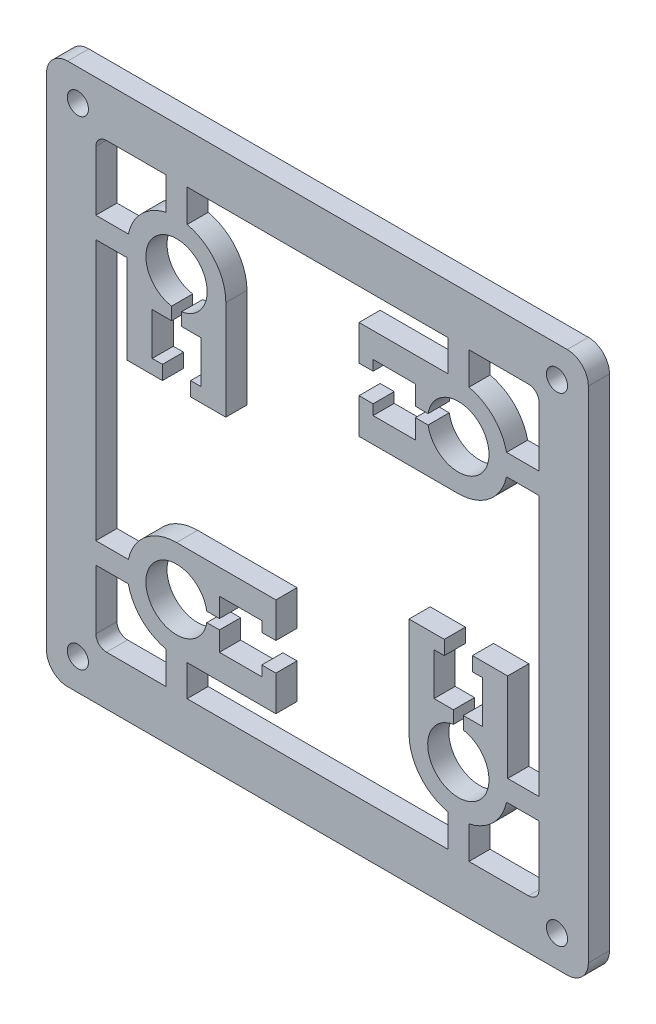
SolidWorks part; units mm, degrees
ref_plane "前基準面" through (0, 0, 0) normal (0, 0, 1) x (1, 0, 0)
ref_plane "上基準面" through (0, 0, 0) normal (0, 1, 0) x (1, 0, 0)
ref_plane "右基準面" through (0, 0, 0) normal (1, 0, 0) x (0, 0, -1)
other "mode"
sketch "草圖1" plane through (0, 0, 0) normal (0, 0, 1) x (1, 0, 0)
  line L0 (0, 0) -> (0, -50.7538) construction
  line L1 (-35.45, 38.45) -> (35.45, 38.45)
  line L2 (-38.45, 35.45) -> (-38.45, -35.45)
  line L3 (-35.45, -38.45) -> (35.45, -38.45)
  line L4 (38.45, 35.45) -> (38.45, -35.45)
  line L5 (0, 0) -> (-82.4302, 0) construction
  line L6 (-29.95, -31.45) -> (-21.5, -31.45)
  line L7 (31.45, 29.95) -> (31.45, 21.5)
  line L8 (-29.95, 31.45) -> (-21.5, 31.45)
  line L9 (-31.45, 29.95) -> (-31.45, 21.5)
  line L10 (-31.45, 31.45) -> (-31.45, -31.45) construction
  line L11 (-31.45, -31.45) -> (31.45, -31.45) construction
  line L12 (31.45, 31.45) -> (31.45, -31.45) construction
  line L13 (-31.45, 31.45) -> (31.45, 31.45) construction
  line L14 (-15.65, 20) -> (18.5, 20) construction
  line L15 (-20, 20) -> (-20, 24.0832) construction
  line L16 (20, 20) -> (20, 43.9064) construction
  line L17 (-18.5, 31.45) -> (18.5, 31.45)
  line L18 (-31.45, 18.5) -> (-31.45, -18.5)
  line L19 (-21.5, 31.45) -> (-21.5, 26.8374)
  line L20 (-13.1626, 18.5) -> (13.1626, 18.5)
  line L21 (-18.5, 31.45) -> (-18.5, 26.8374)
  line L22 (-31.45, 21.5) -> (-26.8374, 21.5)
  line L23 (-13.1626, 21.5) -> (13.1626, 21.5)
  line L24 (-31.45, 18.5) -> (-26.8374, 18.5)
  line L25 (26.8374, 18.5) -> (31.45, 18.5)
  line L26 (18.5, 13.1626) -> (18.5, -13.1626)
  line L27 (18.5, 26.8374) -> (18.5, 31.45)
  line L28 (31.45, 18.5) -> (31.45, -18.5)
  line L29 (21.5, 26.8374) -> (21.5, 31.45)
  line L30 (21.5, 31.45) -> (29.95, 31.45)
  line L31 (26.8374, 21.5) -> (31.45, 21.5)
  line L32 (-31.45, -18.5) -> (-26.8374, -18.5)
  line L33 (-31.45, -21.5) -> (-26.8374, -21.5)
  line L34 (-21.5, -31.45) -> (-21.5, -26.8374)
  line L35 (-18.5, -31.45) -> (-18.5, -26.8374)
  line L36 (-13.1626, -18.5) -> (13.1626, -18.5)
  line L37 (-13.1626, -21.5) -> (13.1626, -21.5)
  line L38 (18.5, -26.8374) -> (18.5, -31.45)
  line L39 (21.5, -26.8374) -> (21.5, -31.45)
  line L40 (26.8374, -21.5) -> (31.45, -21.5)
  line L41 (26.8374, -18.5) -> (31.45, -18.5)
  line L42 (-31.45, -21.5) -> (-31.45, -29.95)
  line L43 (-20, 38.45) -> (-20, 44.9928) construction
  line L44 (-18.5, -31.45) -> (18.5, -31.45)
  line L45 (-21.5, 13.1626) -> (-21.5, -13.1626)
  line L46 (21.5, -31.45) -> (29.95, -31.45)
  line L47 (-18.5, 13.1626) -> (-18.5, -13.1626)
  line L48 (31.45, -21.5) -> (31.45, -29.95)
  line L49 (5.975, 5.975) -> (5.975, -5.975)
  line L51 (21.5, 13.1626) -> (21.5, -13.1626)
  line L52 (-5.975, 5.975) -> (5.975, 5.975)
  line L53 (-5.975, 5.975) -> (-5.975, -5.975)
  line L54 (-5.975, -5.975) -> (5.975, -5.975)
  arc A0 (-21.5, 24.0832) -> (-24.0832, 21.5) centre (-20, 20) ccw construction
  arc A1 (-24.0832, -21.5) -> (-21.5, -24.0832) centre (-20, -20) ccw construction
  arc A2 (18.5, 24.0832) -> (15.9168, 21.5) centre (20, 20) ccw construction
  arc A3 (15.9168, -21.5) -> (18.5, -24.0832) centre (20, -20) ccw construction
  arc A4 (35.45, 38.45) -> (38.45, 35.45) centre (35.45, 35.45) cw
  arc A5 (35.45, -38.45) -> (38.45, -35.45) centre (35.45, -35.45) ccw
  arc A6 (-38.45, -35.45) -> (-35.45, -38.45) centre (-35.45, -35.45) ccw
  arc A7 (-35.45, 38.45) -> (-38.45, 35.45) centre (-35.45, 35.45) ccw
  circle A8 centre (-34, 34) radius 1.5
  circle A9 centre (34, 34) radius 1.5
  circle A10 centre (34, -34) radius 1.5
  circle A11 centre (-34, -34) radius 1.5
  arc A12 (31.45, 29.95) -> (29.95, 31.45) centre (29.95, 29.95) ccw
  arc A13 (-29.95, 31.45) -> (-31.45, 29.95) centre (-29.95, 29.95) ccw
  arc A14 (-24.0832, 18.5) -> (-21.5, 15.9168) centre (-20, 20) ccw construction
  arc A15 (29.95, -31.45) -> (31.45, -29.95) centre (29.95, -29.95) ccw
  arc A16 (-31.45, -29.95) -> (-29.95, -31.45) centre (-29.95, -29.95) ccw
  arc A17 (-31.45, -31.45) -> (-31.45, -31.45) centre (-31.45, -31.45) ccw construction
  arc A18 (31.45, -31.45) -> (31.45, -31.45) centre (31.45, -31.45) ccw construction
  arc A19 (31.45, 31.45) -> (31.45, 31.45) centre (31.45, 31.45) cw construction
  arc A20 (-31.45, 31.45) -> (-31.45, 31.45) centre (-31.45, 31.45) ccw construction
  arc A21 (-15.9168, 21.5) -> (-18.5, 24.0832) centre (-20, 20) ccw construction
  arc A22 (24.0832, 21.5) -> (21.5, 24.0832) centre (20, 20) ccw construction
  arc A23 (15.9168, 18.5) -> (18.5, 15.9168) centre (20, 20) ccw construction
  arc A24 (-18.5, -24.0832) -> (-15.9168, -21.5) centre (-20, -20) ccw construction
  arc A25 (-15.9168, -18.5) -> (-18.5, -15.9168) centre (-20, -20) ccw construction
  arc A26 (21.5, -24.0832) -> (24.0832, -21.5) centre (20, -20) ccw construction
  arc A27 (24.0832, -18.5) -> (21.5, -15.9168) centre (20, -20) ccw construction
  arc A28 (-21.5, -15.9168) -> (-24.0832, -18.5) centre (-20, -20) ccw construction
  arc A29 (18.5, -15.9168) -> (15.9168, -18.5) centre (20, -20) ccw construction
  arc A30 (21.5, 15.9168) -> (24.0832, 18.5) centre (20, 20) ccw construction
  arc A31 (-18.5, 15.9168) -> (-15.9168, 18.5) centre (-20, 20) ccw construction
  arc A32 (-21.5, 26.8374) -> (-26.8374, 21.5) centre (-20, 20) ccw
  arc A33 (-13.1626, 21.5) -> (-18.5, 26.8374) centre (-20, 20) ccw
  arc A34 (-26.8374, 18.5) -> (-21.5, 13.1626) centre (-20, 20) ccw
  arc A35 (-18.5, 13.1626) -> (-13.1626, 18.5) centre (-20, 20) ccw
  circle A36 centre (-20, 20) radius 4.35
  arc A37 (26.8374, 21.5) -> (21.5, 26.8374) centre (20, 20) ccw
  arc A38 (-18.5, -26.8374) -> (-13.1626, -21.5) centre (-20, -20) ccw
  arc A39 (21.5, -26.8374) -> (26.8374, -21.5) centre (20, -20) ccw
  arc A40 (-21.5, -13.1626) -> (-26.8374, -18.5) centre (-20, -20) ccw
  arc A41 (-13.1626, -18.5) -> (-18.5, -13.1626) centre (-20, -20) ccw
  arc A42 (-26.8374, -21.5) -> (-21.5, -26.8374) centre (-20, -20) ccw
  arc A43 (26.8374, -18.5) -> (21.5, -13.1626) centre (20, -20) ccw
  arc A44 (18.5, -13.1626) -> (13.1626, -18.5) centre (20, -20) ccw
  arc A45 (13.1626, -21.5) -> (18.5, -26.8374) centre (20, -20) ccw
  arc A46 (18.5, 26.8374) -> (13.1626, 21.5) centre (20, 20) ccw
  arc A47 (13.1626, 18.5) -> (18.5, 13.1626) centre (20, 20) ccw
  arc A48 (21.5, 13.1626) -> (26.8374, 18.5) centre (20, 20) ccw
  circle A49 centre (20, 20) radius 4.35
  circle A50 centre (-20, -20) radius 4.35
  circle A51 centre (20, -20) radius 4.35
  circle A52 centre (5.975, 5.975) radius 1
  circle A53 centre (5.975, -5.975) radius 1
  point P4 (38.45, 0)
  point P6 (0, 38.45)
  point P26 (-38.45, -38.45)
  point P29 (-38.45, 38.45)
  point P151 (0, 5.975)
  dimension "D3" = 8.7
  dimension "D5" = 3
  dimension "D6" = 3
  dimension "D10" = 1.5
  dimension "D11" = 1.5
  dimension "D15" = 11.95
  dimension "D16" = 2
  dimension "D1" = 20
  dimension "D2" = 20
  dimension "D4" = 76.9
  dimension "D7" = 14
  dimension "D8" = 14
  dimension "D12" = 3
  dimension "D13" = 3
  dimension "D14" = 3
  dimension "D9" = 7
extrude "填料-伸長1" add sketch "草圖1" along normal blind 3 contours L1 A7 L2 A6 L3 A5 L4 A4 A51 A50 A49 L27 A46 L23 A33 L21 L17 L37 A45 L38 L44 L35 A38 L33 A42 L34 L6 A16 L42 L45 A40 L32 L18 L24 A34 L39 A39 L40 L48 A15 L46 L31 region at (0, 37.3625, 0)
sketch "草圖2" plane through (0, 0, 0) normal (0, 0, -1) x (-1, 0, 0)
  line L0 (20, 24.35) -> (20, 15.65) construction
  line L1 (13, 20) -> (13, 5.9)
  line L2 (16.55, 13.9092) -> (16.55, 7.9)
  line L3 (23.45, 13.9092) -> (23.45, 7.9)
  line L4 (15.0092, 3.9) -> (24.9908, 3.9)
  line L5 (16.55, 7.9) -> (23.45, 7.9)
  line L6 (27, 20) -> (27, 5.9)
  line L7 (23.45, 7.9) -> (23.4495, 7.8885)
  line L8 (15.0092, 3.9) -> (13, 5.9)
  line L9 (24.9908, 3.9) -> (27, 5.9)
  arc A0 (13, 20) -> (16.55, 13.9092) centre (20, 20) ccw
  arc A1 (23.45, 13.9092) -> (27, 20) centre (20, 20) ccw
  circle A2 centre (20, 20) radius 4.35 construction
  arc A3 (13.1626, 18.5) -> (18.5, 13.1626) centre (20, 20) ccw construction
  arc A4 (21.5, 13.1626) -> (26.8374, 18.5) centre (20, 20) ccw construction
  dimension "D1" = 6.9
  dimension "D2" = 6.0092
  dimension "D3" = 14
  dimension "D5" = 16.1
extrude "填料-伸長3" add sketch "草圖2" against normal blind 3 contours A1 L5 A0 L6 region at (-13.7679, 16.3677, 0)
sketch "草圖4" plane through (0, 0, 0) normal (0, 0, -1) x (-1, 0, 0)
  line L0 (16.55, 7.8992) -> (13, 7.8992)
  line L1 (16.55, 7.8992) -> (18, 7.8992)
  line L2 (16.55, 7.8992) -> (16.55, 13.9092)
  line L3 (16.55, 13.9092) -> (19.3, 13.9092)
  line L4 (23.45, 7.8992) -> (23.45, 13.9092)
  line L5 (13, 18.5) -> (13, 5.9) construction
  line L6 (20, 24.35) -> (20, 15.65) construction
  line L8 (19.3, 13.9092) -> (19.3, 16.4092)
  line L9 (19.3, 16.4092) -> (20.7, 16.4092)
  line L10 (20.7, 13.9092) -> (20.7, 16.4092)
  line L11 (13, 7.8992) -> (13, -2.1008)
  line L12 (20.7, 13.9092) -> (23.45, 13.9092)
  line L13 (31.45, 7.8992) -> (31.45, -2.1008)
  line L14 (18, 7.8992) -> (18, 1.8992)
  line L15 (18, 1.8992) -> (22, 1.8992)
  line L16 (22, 7.8992) -> (22, 1.8992)
  line L17 (22, 7.8992) -> (23.45, 7.8992)
  line L18 (23.45, 7.8992) -> (31.45, 7.8992)
  line L19 (31.45, 18.5) -> (31.45, -18.5) construction
  line L20 (13, 5.9) -> (31.45, 5.9)
  line L21 (18.5, -2.1008) -> (18.5, -13)
  line L22 (18.5, -2.1008) -> (18.5, -13)
  line L25 (31.45, -2.1008) -> (21.5, -2.1008)
  line L26 (21.5, 3.9) -> (21.5, -13.1626) construction
  line L27 (18.5, -2.1008) -> (13, -2.1008)
  line L28 (31.45, 18.5) -> (31.45, -18.5) construction
  line L29 (21.5, -13.1626) -> (21.5, -2.1008)
  line L30 (18.5, -13) -> (20, -13)
  circle A0 centre (20, 20) radius 4.35 construction
  arc A1 (21.5, -13.1626) -> (18.5, -13.1626) centre (20, -20) ccw construction
  arc A2 (21.5, -13.1626) -> (20, -13) centre (20, -20) ccw
  point P36 (20, 1.8992)
  dimension "D1" = 6.01
  dimension "D2" = 4
  dimension "D3" = 1.4
  dimension "D4" = 2.5
  dimension "D5" = 6
  dimension "D6" = 4
ref_axis "基準軸3" through (0, 0, -0.15) along (0, 0, 1)
extrude "除料-伸長2" cut sketch "草圖4" against normal through all contours L16 L17 L4 L12 L10 L9 L8 L3 L2 L1 L14 L15 | L14 L15 L16 | A1 L13 L20 L16 L15 L14 L11 region at (-20, 10.5808, 0) region at (-21.9985, -0.1821, 0) region at (-20, 3.8996, 0)
pattern_circular "環狀複製排列2" count 4 every 90 about axis through (0, 0, -0.15) along (0, 0, 1) of "填料-伸長3", "除料-伸長2"
